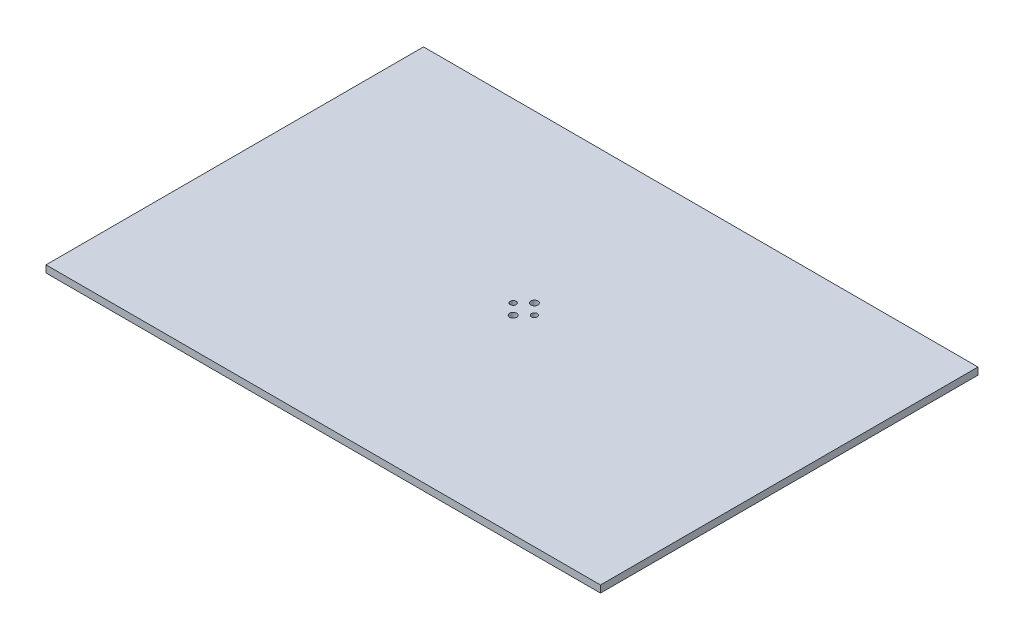
SolidWorks part; units mm, degrees
ref_plane "Front" through (0, 0, 0) normal (0, 0, 1) x (1, 0, 0)
ref_plane "Top" through (0, 0, 0) normal (0, 1, 0) x (1, 0, 0)
ref_plane "Right" through (0, 0, 0) normal (1, 0, 0) x (0, 0, -1)
sketch "Sketch1" plane through (0, 0, 0) normal (0, 1, 0) x (1, 0, 0)
  line L1 (0, 0) -> (470, 0)
  line L2 (0, 0) -> (0, 320)
  line L3 (0, 320) -> (470, 320)
  line L4 (470, 0) -> (470, 320)
  dimension "D1" = 320
  dimension "D2" = 470
extrude "Boss-Extrude1" add sketch "Sketch1" along normal blind 6
sketch "Sketch2" plane through (0, 6, 0) normal (0, 1, 0) x (1, 0, 0)
  line L0 (470, 320) -> (0, 320) construction
  line L1 (235, 179) -> (235, 161) construction
  line L2 (226, 170) -> (244, 170) construction
  line L3 (470, 0) -> (470, 320) construction
  circle A1 centre (235, 161) radius 3
  circle A2 centre (235, 179) radius 3
  circle A3 centre (226, 170) radius 2.5
  circle A4 centre (244, 170) radius 2.5
  point P0 (235, 170)
  dimension "D1" = 9
  dimension "D4" = 6
  dimension "D5" = 5
  dimension "D7" = 18
  dimension "D8" = 150
  dimension "D3" = 9
  dimension "D2" = 235
  dimension "D6" = 18
extrude "Cut-Extrude1" cut sketch "Sketch2" against normal blind 6
